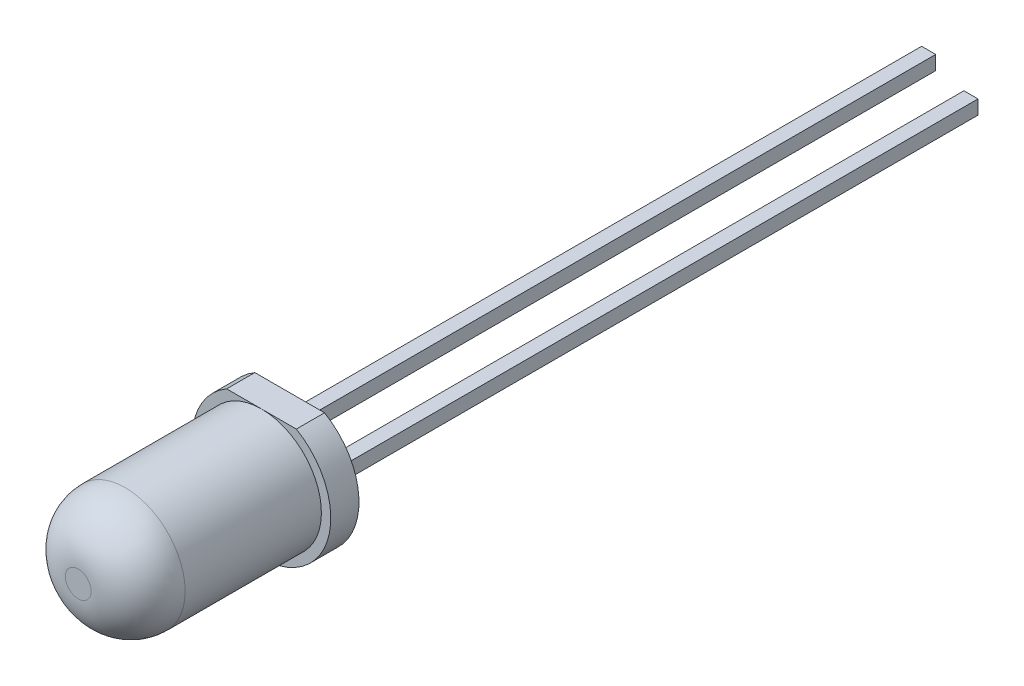
SolidWorks part; units mm, degrees
ref_plane "Płaszczyzna przednia" through (0, 0, 0) normal (0, 0, 1) x (1, 0, 0)
ref_plane "Płaszczyzna górna" through (0, 0, 0) normal (0, 1, 0) x (1, 0, 0)
ref_plane "Płaszczyzna prawa" through (0, 0, 0) normal (1, 0, 0) x (0, 0, -1)
sketch "Szkic2" plane through (0, 0, 0) normal (0, 0, 1) x (1, 0, 0)
  circle A0 centre (0, 0) radius 2.95
  dimension "D1" = 5.9
extrude "Dodanie-wyciągnięcie1" add sketch "Szkic2" along normal blind 1.2
sketch "Szkic3" plane through (0, 0, 1.2) normal (0, 0, 1) x (1, 0, 0)
  circle A0 centre (0, 0) radius 2.55
extrude "Dodanie-wyciągnięcie2" add sketch "Szkic3" along normal blind 7.8
fillet "Zaokrąglenie2" radius 2 1 edges at (2.55, 0, 9)
sketch "Szkic4" plane through (0, 0, 1.2) normal (0, 0, 1) x (1, 0, 0)
  line L0 (-2.1418, 2.55) -> (2.1418, 2.55)
  line L1 (0, 2.55) -> (0, 3.3003)
  line L2 (2.1418, 2.55) -> (2.1418, 3.3003)
  line L3 (-2.1418, 3.3003) -> (2.1418, 3.3003)
  line L4 (-2.1418, 2.55) -> (-2.1418, 3.3003)
  circle A0 centre (0, 0) radius 2.55 construction
extrude "Wytnij-wyciągnięcie1" cut sketch "Szkic4" against normal blind 7.8 contours L4 L3 L2 L0
sketch "Szkic5" plane through (0, 0, 0) normal (1, 0, 0) x (0, 0, -1)
  line L0 (0, 0) -> (-15, 0) construction
  dimension "D1" = 15
sketch "Szkic6" plane through (0, 0, 0) normal (1, 0, 0) x (0, 0, -1)
  line L0 (0, 0) -> (-15, 0) construction
  line L1 (-3.1, -0.5) -> (-3.3, -0.5)
  line L2 (-3.1, -0.5) -> (-3.1, 0.5)
  line L3 (-3.1, 0.5) -> (-3.3, 0.5)
  line L4 (-3.3, -0.5) -> (-3.3, 0.5)
  line L5 (-3.1, -0.5) -> (-3.3, 0.5) construction
  line L6 (-3.1, 0.5) -> (-3.3, -0.5) construction
  line L7 (-9, 0.55) -> (-9, -0.55) construction
  point P0 (-3.2, 0)
  dimension "D1" = 0.2
  dimension "D2" = 1
  dimension "D3" = 5.7
extrude "Dodanie-wyciągnięcie5" add sketch "Szkic6" along normal blind 0.25 and the other way blind 0.25 separate body
sketch "Szkic7" plane through (0, 0, 0) normal (0, 0, -1) x (-1, 0, 0)
  line L0 (3.245, 0) -> (-3.245, 0) construction
  line L1 (-0.3, 0.97) -> (0.3, 0.97)
  line L2 (-0.3, 0.97) -> (-0.3, 1.57)
  line L3 (-0.3, 1.57) -> (0.3, 1.57)
  line L4 (0.3, 0.97) -> (0.3, 1.57)
  line L5 (-0.3, 0.97) -> (0.3, 1.57) construction
  line L6 (-0.3, 1.57) -> (0.3, 0.97) construction
  line L7 (-0.3, -1.57) -> (0.3, -1.57)
  line L8 (0.3, -0.97) -> (0.3, -1.57)
  line L9 (-0.3, -0.97) -> (0.3, -0.97)
  line L10 (-0.3, -0.97) -> (-0.3, -1.57)
  point P0 (0, 1.27)
  dimension "D1" = 0.6
  dimension "D2" = 0.6
  dimension "D3" = 1.27
extrude "Dodanie-wyciągnięcie6" add sketch "Szkic7" along normal blind 29 contours L9 L10 L7 L8 | L2 L1 L4 L3 region at (0, -1.27, 0)
sketch "Szkic8" plane through (0, 0, -29) normal (0, 0, -1) x (-1, 0, 0)
  line L1 (-0.4307, 0.8887) -> (0.4307, 0.8887)
  line L2 (-0.4307, 0.8887) -> (-0.4307, 1.7952)
  line L3 (-0.4307, 1.7952) -> (0.4307, 1.7952)
  line L4 (0.4307, 0.8887) -> (0.4307, 1.7952)
  line L5 (-0.4307, 0.8887) -> (0.4307, 1.7952) construction
  line L6 (-0.4307, 1.7952) -> (0.4307, 0.8887) construction
  point P0 (0, 1.342)
extrude "Wytnij-wyciągnięcie2" cut sketch "Szkic8" against normal blind 1.8
